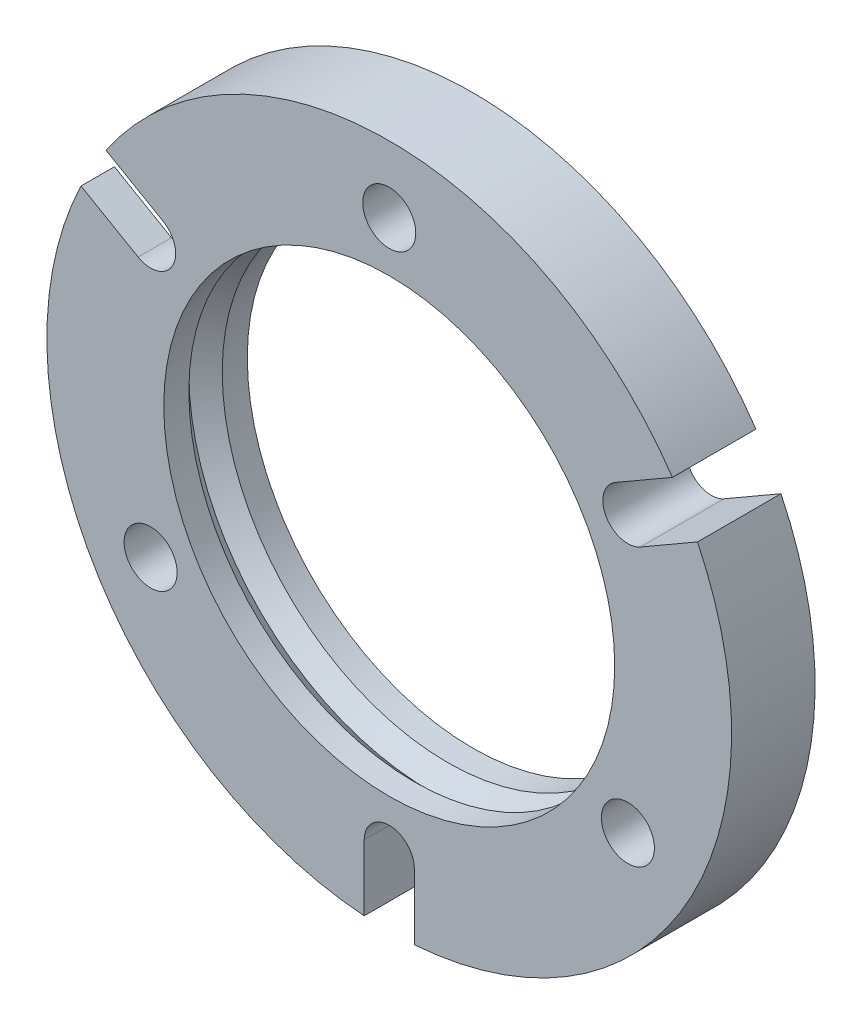
SolidWorks part; units mm, degrees
material "Polyetheretherketone (PEEK)"
ref_plane "Front Plane" through (0, 0, 0) normal (0, 0, 1) x (1, 0, 0)
ref_plane "Top Plane" through (0, 0, 0) normal (0, 1, 0) x (1, 0, 0)
ref_plane "Right Plane" through (0, 0, 0) normal (1, 0, 0) x (0, 0, -1)
sketch "Sketch1" plane through (0, 0, 0) normal (0, 0, 1) x (1, 0, 0)
  circle A0 centre (0, 0) radius 20.5
  circle A1 centre (0, 0) radius 13.5
  circle A2 centre (0, 16.5) radius 1.5875
  circle A3 centre (14.2894, -8.25) radius 1.5875
  circle A4 centre (-14.2894, -8.25) radius 1.5875
  circle A5 centre (0, 0) radius 16.5 construction
  dimension "D1" = 27
  dimension "D2" = 3.175
  dimension "D4" = 41
  dimension "D3" = 33
extrude "Extrude1" add sketch "Sketch1" along normal blind 5
sketch "Sketch2" plane through (0, 0, 5) normal (0, 0, 1) x (1, 0, 0)
  line L0 (1.5, -16.5) -> (1.5, -20.445)
  line L1 (-1.5, -16.5) -> (-1.5, -20.445)
  circle A0 centre (0, 0) radius 16.5 construction
  circle A1 centre (0, 0) radius 20.5
  circle A2 centre (0, 0) radius 20.5
  circle A3 centre (0, -16.5) radius 1.5
  circle M4 centre (0, 0) radius 20.5
  dimension "D2" = 3
  dimension "D1" = 0
extrude "Cut-Extrude1" cut sketch "Sketch2" against normal through all contours A3 L1 L0 M4 | A3 region at (0, -16.5, 5) region at (0, -19.06, 5)
sketch "Sketch3" plane through (0, 0, 0) normal (0, 1, 0) x (1, 0, 0)
  line L0 (0, -5) -> (0, 0) construction
  line L1 (-13.5, -5) -> (13.5, -5) construction
  line L2 (0, -5) -> (-9, -5) construction
  line L3 (-20.5, -5) -> (20.5, -5) construction
  line L4 (-9, -5) -> (-9, 0)
  line L5 (13.5, 0) -> (-13.5, 0) construction
  line L6 (20.5, 0) -> (-20.5, 0) construction
  line L7 (-12.4314, -5) -> (-9, -5)
  line L9 (0, 0) -> (0, 5.2553) construction
  line L10 (0, 5.2553) -> (-20.5, 5.2553)
  line L11 (-20.5, 5.2553) -> (-20.5, 0)
  line L12 (-20.5, 0) -> (0, 0)
  line L13 (-9, 0) -> (-9, 5.2553)
  line L14 (-9, 5.2553) -> (-12.4314, -5)
  line L15 (-15.8769, -5) -> (-12.7019, -5) construction
  dimension "D1" = 9
  dimension "D2" = 18.5
  dimension "D3" = 5.2553
revolve "Cut-Revolve1" [suppressed] cut sketch "Sketch3" angle 360 about L0
sketch "Sketch4" plane through (0, 0, 0) normal (0, 1, 0) x (1, 0, 0)
  line L0 (0, 0) -> (0, -5) construction
  line L1 (-13.5, -5) -> (13.5, -5) construction
  line L2 (-13.5, 0) -> (-13.5, -5)
  line L3 (13.5, 0) -> (-13.5, 0) construction
  line L4 (-12.7019, 0) -> (-15.8769, 0) construction
  line L5 (0, -2.5) -> (-13.5, -2.5) construction
  line L6 (-13.5, -2.5) -> (-14.5, -2.5)
  line L7 (-14.5, -2.5) -> (-13.5, -1.5)
  line L8 (-14.5, -2.5) -> (-13.5, -3.5)
  dimension "D1" = 13.5
  dimension "D2" = 45
  dimension "D3" = 1
revolve "Cut-Revolve3" cut sketch "Sketch4" angle 360 about L0 region at (-13.8333, 0, 2.1667) region at (-13.8333, 0, 2.8333)
ref_axis "Axis1" through (0, 0, 5) along (0, 0, -1)
pattern_circular "CirPattern1" count 3 over 360 about axis through (0, 0, 5) along (0, 0, -1) of "Cut-Extrude1"
sketch "Sketch5" plane through (0, 0, 0) normal (0, 0, -1) x (-1, 0, 0)
  line L0 (0, 0) -> (14.2894, 8.25) construction
  line L1 (0, 0) -> (15.9378, 4.2705) construction
  line L2 (14.552, 3.6965) -> (12.9036, 7.676)
  line L3 (16.2597, 2.8055) -> (20.1698, 3.6648)
  line L6 (-16.9559, 11.5216) -> (-13.5394, 9.549)
  line L7 (-15.0394, 6.951) -> (-18.4559, 8.9235)
  line L8 (-1.5, -20.445) -> (-1.5, -16.5)
  line L9 (1.5, -16.5) -> (1.5, -20.445)
  line L10 (18.4559, 8.9235) -> (15.0394, 6.951)
  line L11 (13.5394, 9.549) -> (16.9559, 11.5216)
  line L12 (-16.9559, 11.5216) -> (-13.5394, 9.549)
  line L13 (-15.0394, 6.951) -> (-18.4559, 8.9235)
  line L14 (-1.5, -20.445) -> (-1.5, -16.5)
  line L15 (1.5, -16.5) -> (1.5, -20.445)
  line L16 (18.4559, 8.9235) -> (15.0394, 6.951)
  line L17 (13.5394, 9.549) -> (16.9559, 11.5216)
  circle A0 centre (0, 0) radius 16.5 construction
  circle A1 centre (15.9378, 4.2705) radius 1.5
  arc A6 (-15.0394, 6.951) -> (-13.5394, 9.549) centre (-14.2894, 8.25) ccw
  arc A7 (-18.4559, 8.9235) -> (-1.5, -20.445) centre (0, 0) ccw
  arc A8 (1.5, -16.5) -> (-1.5, -16.5) centre (0, -16.5) ccw
  arc A9 (1.5, -20.445) -> (18.4559, 8.9235) centre (0, 0) ccw
  arc A10 (13.5394, 9.549) -> (15.0394, 6.951) centre (14.2894, 8.25) ccw
  arc A11 (16.9559, 11.5216) -> (-16.9559, 11.5216) centre (0, 0) ccw
  arc A12 (-15.0394, 6.951) -> (-13.5394, 9.549) centre (-14.2894, 8.25) ccw
  arc A13 (-18.4559, 8.9235) -> (-1.5, -20.445) centre (0, 0) ccw
  arc A14 (1.5, -16.5) -> (-1.5, -16.5) centre (0, -16.5) ccw
  arc A15 (1.5, -20.445) -> (18.4559, 8.9235) centre (0, 0) ccw
  arc A16 (13.5394, 9.549) -> (15.0394, 6.951) centre (14.2894, 8.25) ccw
  arc A17 (16.9559, 11.5216) -> (-16.9559, 11.5216) centre (0, 0) ccw
  arc M24 (1.5, -20.445) -> (18.4559, 8.9235) centre (0, 0) ccw
  line M25 (18.4559, 8.9235) -> (15.0394, 6.951)
  arc M26 (15.0394, 6.951) -> (13.5394, 9.549) centre (14.2894, 8.25) cw
  dimension "D3" = 3
  dimension "D2" = 15
  dimension "D1" = 0
extrude "Cut-Extrude2" cut sketch "Sketch5" against normal blind 3 contours A1 | A1 L3 L2 M24 M25 M26 region at (-17.3223, 5.9161, 0) region at (-15.9378, 4.2705, 0)
